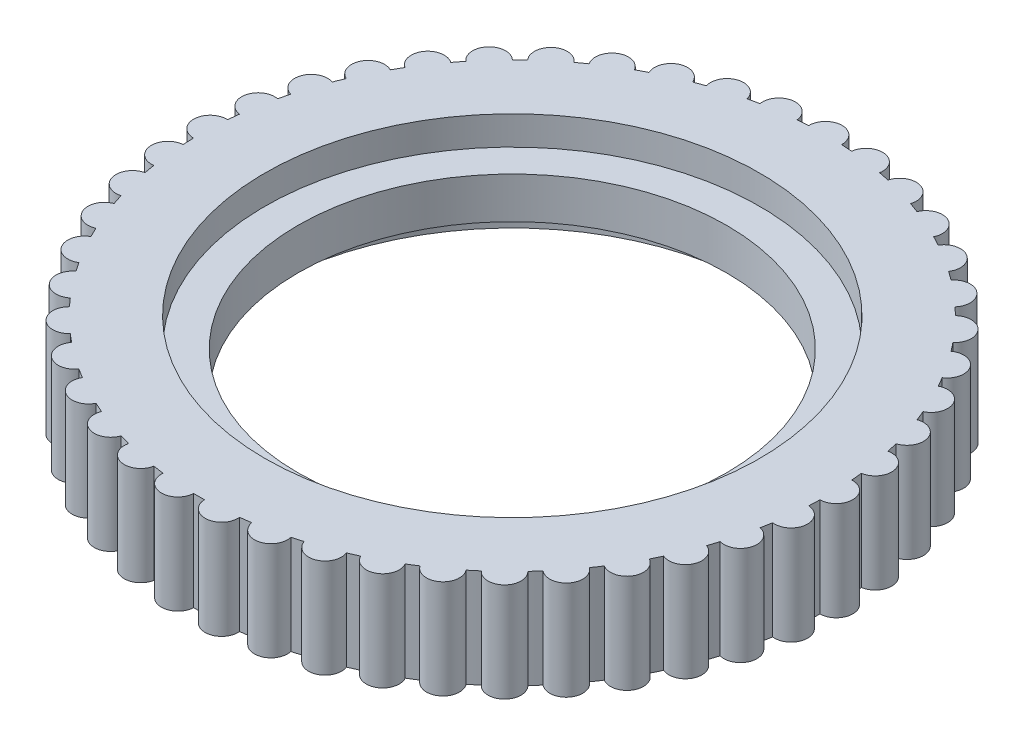
SolidWorks part; units mm, degrees
ref_plane "Front Plane" through (0, 0, 0) normal (0, 0, 1) x (1, 0, 0)
ref_plane "Top Plane" through (0, 0, 0) normal (0, 1, 0) x (1, 0, 0)
ref_plane "Right Plane" through (0, 0, 0) normal (1, 0, 0) x (0, 0, -1)
sketch "Sketch1" plane through (0, 0, 0) normal (0, 1, 0) x (1, 0, 0)
  line L0 (0, 19) -> (0, 20) construction
  circle A0 centre (0, 0) radius 13
  circle A1 centre (0, 0) radius 15
  circle A2 centre (0, 0) radius 19
  circle A3 centre (0, 19) radius 1
  circle A4 centre (2.6443, 18.8151) radius 1
  circle A5 centre (5.2371, 18.264) radius 1
  circle A6 centre (7.728, 17.3574) radius 1
  circle A7 centre (10.0685, 16.1129) radius 1
  circle A8 centre (12.213, 14.5548) radius 1
  circle A9 centre (14.1198, 12.7135) radius 1
  circle A10 centre (15.7517, 10.6247) radius 1
  circle A11 centre (17.0771, 8.3291) radius 1
  circle A12 centre (18.0701, 5.8713) radius 1
  circle A13 centre (18.7113, 3.2993) radius 1
  circle A14 centre (18.9884, 0.6631) radius 1
  circle A15 centre (18.8959, -1.986) radius 1
  circle A16 centre (18.4356, -4.5965) radius 1
  circle A17 centre (17.6165, -7.1175) radius 1
  circle A18 centre (16.4545, -9.5) radius 1
  circle A19 centre (14.9722, -11.6976) radius 1
  circle A20 centre (13.1985, -13.6675) radius 1
  circle A21 centre (11.1679, -15.3713) radius 1
  circle A22 centre (8.92, -16.776) radius 1
  circle A23 centre (6.4984, -17.8542) radius 1
  circle A24 centre (3.9503, -18.5848) radius 1
  circle A25 centre (1.3254, -18.9537) radius 1
  circle A26 centre (-1.3254, -18.9537) radius 1
  circle A27 centre (-3.9503, -18.5848) radius 1
  circle A28 centre (-6.4984, -17.8542) radius 1
  circle A29 centre (-8.92, -16.776) radius 1
  circle A30 centre (-11.1679, -15.3713) radius 1
  circle A31 centre (-13.1985, -13.6675) radius 1
  circle A32 centre (-14.9722, -11.6976) radius 1
  circle A33 centre (-16.4545, -9.5) radius 1
  circle A34 centre (-17.6165, -7.1175) radius 1
  circle A35 centre (-18.4356, -4.5965) radius 1
  circle A36 centre (-18.8959, -1.986) radius 1
  circle A37 centre (-18.9884, 0.6631) radius 1
  circle A38 centre (-18.7113, 3.2993) radius 1
  circle A39 centre (-18.0701, 5.8713) radius 1
  circle A40 centre (-17.0771, 8.3291) radius 1
  circle A41 centre (-15.7517, 10.6247) radius 1
  circle A42 centre (-14.1198, 12.7135) radius 1
  circle A43 centre (-12.213, 14.5548) radius 1
  circle A44 centre (-10.0685, 16.1129) radius 1
  circle A45 centre (-7.728, 17.3574) radius 1
  circle A46 centre (-5.2371, 18.264) radius 1
  circle A47 centre (-2.6443, 18.8151) radius 1
  point P99 (0, 0)
  dimension "D1" = 2
  dimension "D2" = 4
  dimension "D3" = 26
  dimension "D4" = 1
  dimension "D5" = 45
extrude "Boss-Extrude1" add sketch "Sketch1" along normal blind 6 contours A2 A43 | A2 A43 | A2 A44 | A2 A31 | A2 A28 | A2 A15 | A2 A21 | A47 A2 A46 A45 A44 A43 A42 A41 A40 A39 A38 A37 A36 A35 A34 A33 A32 A31 A30 A29 A28 A27 A26 A25 A24 A23 A22 | A44 | A45 | A46 | A47 | A3 | A4 | A5 | A6 | A7 | A8 | A42 | A41 | A40 | A39 | A38 | A37 | A36 | A35 | A34 | A33 | A32 | A30 | A31 | A29 | A28 | A27 | A26 | A25 | A9 | A10 | A11 | A12 | A13 | A14 | A15 | A16 | A17 | A18 | A19 | A20 | A21 | A22 | A23 | A24 region at (17.4522, 0, -0.6094) region at (19.3133, 0, 2.0299) region at (11.4146, 0, 15.7108) region at (-6.6419, 0, 18.2485) region at (-10.2908, 0, -16.4688) region at (-11.9371, 0, -14.2261) region at (-12.4827, 0, -14.8763) region at (-13.49, 0, 13.9693)
extrude "Boss-Extrude2" add sketch "Sketch1<3>" along normal blind 2.5 from offset 1.75 contours A1 A0 region at (-14.5757, 0, 0)
sketch "Sketch1<3>" plane through (0, 0, 0) normal (0, 1, 0) x (1, 0, 0) same geometry as "Sketch1"
